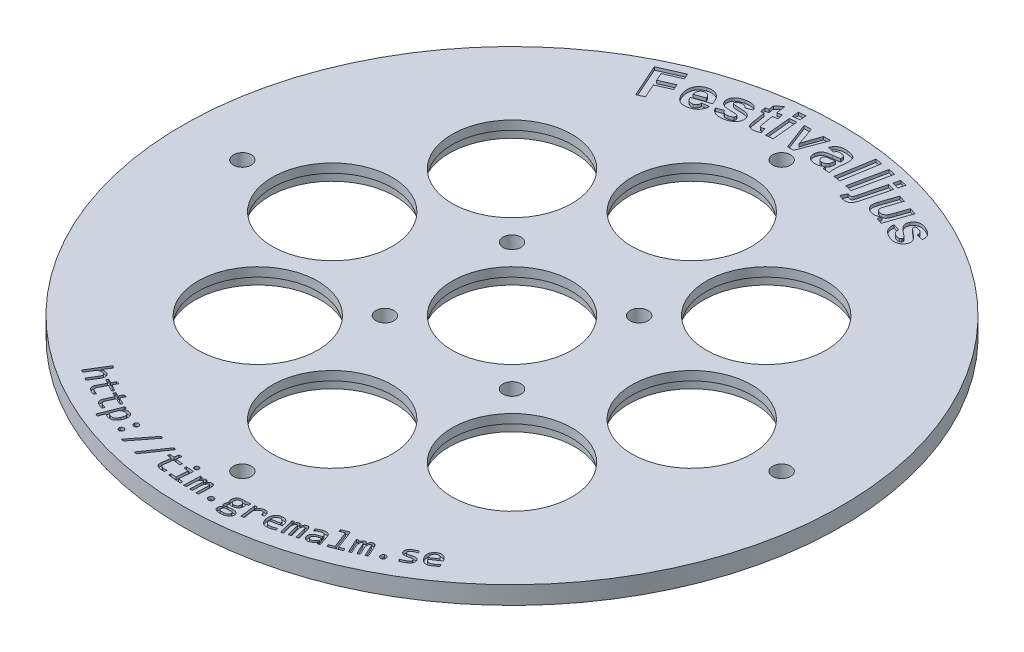
SolidWorks part; units mm, degrees
material "Acrylic (Medium-high impact)"
ref_plane "Front Plane" through (0, 0, 0) normal (0, 0, 1) x (1, 0, 0)
ref_plane "Top Plane" through (0, 0, 0) normal (0, 1, 0) x (1, 0, 0)
ref_plane "Right Plane" through (0, 0, 0) normal (1, 0, 0) x (0, 0, -1)
sketch "Sketch2" plane through (0, 0, 0) normal (0, 1, 0) x (1, 0, 0)
  line L0 (0, 0) -> (0, 30) construction
  circle A0 centre (0, 0) radius 55
  circle A1 centre (0, 30) radius 10
  circle A2 centre (0, 0) radius 10
  circle A3 centre (21.2132, 21.2132) radius 10
  circle A4 centre (30, 0) radius 10
  circle A5 centre (21.2132, -21.2132) radius 10
  circle A6 centre (0, -30) radius 10
  circle A7 centre (-21.2132, -21.2132) radius 10
  circle A8 centre (-30, 0) radius 10
  circle A9 centre (-21.2132, 21.2132) radius 10
  point P22 (0, 0)
  dimension "D1" = 110
  dimension "D3" = 20
  dimension "D2" = 30
sketch "Sketch1" plane through (0, 0, 0) normal (0, 1, 0) x (1, 0, 0)
  line L0 (0, 0) -> (0, 45) construction
  line L1 (0, 0) -> (39.507, 0) construction
  line L2 (0, 0) -> (-10.6066, 10.6066) construction
  circle A0 centre (45, 0) radius 1.5
  circle A1 centre (0, 45) radius 1.5
  circle A2 centre (-10.6066, 10.6066) radius 1.5
  circle A3 centre (0, -45) radius 1.5
  circle A4 centre (-45, 0) radius 1.5
  circle A5 centre (10.6066, 10.6066) radius 1.5
  circle A6 centre (10.6066, -10.6066) radius 1.5
  circle A7 centre (-10.6066, -10.6066) radius 1.5
  point P17 (0, 0)
  point P24 (0, 0)
  dimension "D5" = 3
  dimension "D2" = 45
  dimension "D3" = 45
  dimension "D4" = 15
extrude "Lens Holder Boss-Extrude1" add sketch "Sketch2" along normal blind 3
sketch "Sketch3" plane through (0, 0, 0) normal (0, 1, 0) x (1, 0, 0)
  circle A0 centre (0, 0) radius 10.5
  circle A1 centre (0, 30) radius 10.5
  circle A2 centre (21.2132, 21.2132) radius 10.5
  circle A3 centre (30, 0) radius 10.5
  circle A4 centre (21.2132, -21.2132) radius 10.5
  circle A5 centre (0, -30) radius 10.5
  circle A6 centre (-21.2132, -21.2132) radius 10.5
  circle A7 centre (-30, 0) radius 10.5
  circle A8 centre (-21.2132, 21.2132) radius 10.5
  point P22 (0, 0)
  dimension "D1" = 21
extrude "Lens Groove Cut-Extrude1" cut sketch "Sketch3" along normal blind 1.5
extrude "Screw Holes Cut-Extrude2" cut sketch "Sketch1" along normal up to surface (3 mm away) up to face at (-30, 3, 10)
sketch "Sketch4" plane through (0, 3, 0) normal (0, 1, 0) x (1, 0, 0)
  arc A0 (30.6594, -42) -> (-30.6594, -42) centre (0, 0) cw construction
  circle A1 centre (0, 0) radius 55 construction
  arc A2 (-22.1867, 42) -> (22.1867, 42) centre (0, 0) cw construction
  text T0 "http://tim.gremalm.se" font "Consolas for Powerline FixedD" height 3.5
  text T1 "Festivalljus" font "Arial" height in points 24
  dimension "D1" = 3
  dimension "D3" = 7.5
  dimension "D2" = 42
  dimension "D4" = 42
extrude "Text Cut-Extrude3" cut sketch "Sketch4" against normal blind 0.5
